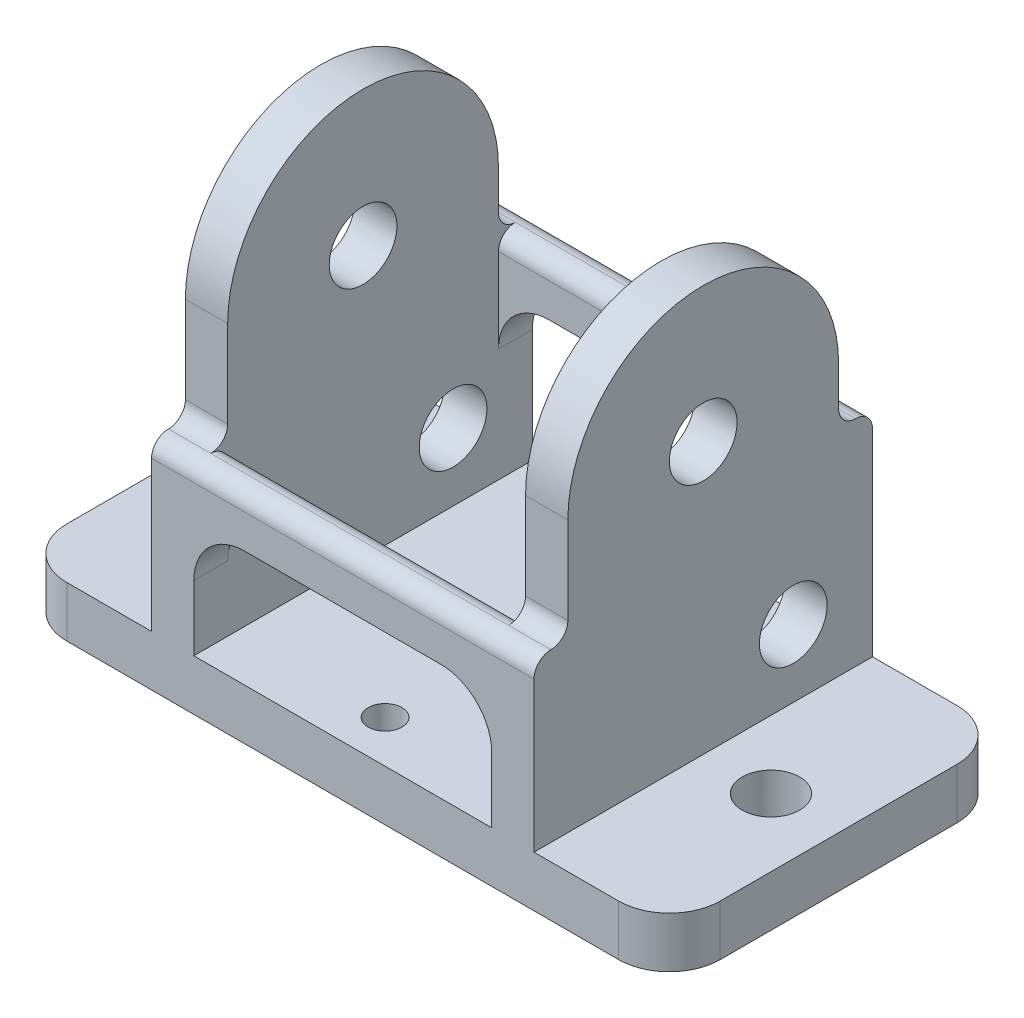
SolidWorks part; units mm, degrees
ref_plane "Plan de face" through (0, 0, 0) normal (0, 0, 1) x (1, 0, 0)
ref_plane "Plan de dessus" through (0, 0, 0) normal (0, 1, 0) x (1, 0, 0)
ref_plane "Plan de droite" through (0, 0, 0) normal (1, 0, 0) x (0, 0, -1)
sketch "Esquisse2" plane through (0, 0, 0) normal (0, 0, 1) x (1, 0, 0)
  line L0 (0, 1.475) -> (0, -1.8592) construction
  line L1 (-2.1467, 0) -> (3.7613, 0) construction
  line L4 (8.8, 2) -> (11.3, 2)
  line L5 (11.3, 2) -> (11.3, 8)
  line L6 (11.3, 8) -> (8.8, 8)
  line L7 (8.8, 8) -> (8.8, 2)
  dimension "D1" = 2.5
  dimension "D2" = 2
  dimension "D5" = 8
  dimension "D6" = 8.8
revolve "Révolution1" add sketch "Esquisse2" angle 360 about L1
sketch "Esquisse3" plane through (11.3, 0, 0) normal (1, 0, 0) x (0, 0, -1)
  line L1 (-10, -19) -> (10, -19)
  line L3 (-10, -16) -> (10, -16)
  line L4 (3.318, 0) -> (3.318, -16) construction
  line L5 (8, 0) -> (8, -6.3137)
  line L6 (5.6569, -5.6569) -> (12.7279, 1.4142) construction
  line L7 (0, -8) -> (10, -8) construction
  line L8 (8, -3.3137) -> (10, -3.3137)
  line L9 (10, -3.3137) -> (10, -19)
  line L10 (8, -6.3137) -> (10, -6.3137)
  line L11 (-5.6569, -5.6569) -> (-12.7279, 1.4142) construction
  line L12 (-8, -6.1421) -> (-10, -6.1421)
  line L13 (-12.7279, -1.4142) -> (-6.1421, -8) construction
  line L14 (-8, 0) -> (-8, -9.1421)
  line L15 (-8, -9.1421) -> (-10, -9.1421)
  line L16 (-10, -6.1421) -> (-10, -19)
  circle A0 centre (0, 0) radius 8 construction
  arc A1 (-8, 0) -> (8, 0) centre (0, 0) ccw
  circle A2 centre (0, 0) radius 3.318 construction
  circle A3 centre (5.318, -12) radius 2
  circle M5 centre (0, 0) radius 8
  dimension "D3" = 6.636
  dimension "D4" = 4
  dimension "D5" = 2
  dimension "D1" = 2
  dimension "D2" = 3
  dimension "D6" = 45
  dimension "D7" = 10
  dimension "D8" = 2
  dimension "D9" = 3
  dimension "D10" = 2
  dimension "D11" = 45
  dimension "D12" = 2
  dimension "D13" = 3
extrude "Boss.-Extru.1" add sketch "Esquisse3" against normal up to surface (2.5 mm away) contours L3 L1 | L3 M5 | L5 L10 L9 L8 | L12 L16 L15 L14 region at (11.3, -17.5, 0) region at (11.3, -11.0485, 0.0904) region at (11.3, -7.6421, 9) region at (11.3, -4.8137, -9) up to face at (8.8, 0, 2)
extrude "Boss.-Extru.2" add sketch "Esquisse3<3>" against normal up to surface (11.3 mm away) from surface contours L3 L1 | L5 L10 L9 L8 | L12 L16 L15 L14 region at (11.3, -17.5, 0) region at (11.3, -7.6421, 9) region at (11.3, -4.8137, -9) up to plane "Plan de droite" starting at face at (8.8, 0, 2)
sketch "Esquisse3<3>" plane through (11.3, 0, 0) normal (1, 0, 0) x (0, 0, -1) same geometry as "Esquisse3"
extrude "Boss-Extrude1" add sketch "Esquisse3<5>" along normal blind 8 contours L3 L16 L1 L9 region at (11.3, -17.5, 0)
sketch "Esquisse3<5>" plane through (11.3, 0, 0) normal (1, 0, 0) x (0, 0, -1) same geometry as "Esquisse3"
sketch "Sketch4" plane through (0, -16, 0) normal (0, 1, 0) x (1, 0, 0)
  line L0 (19.3, 10) -> (11.3, 10) construction
  circle A0 centre (15.3, 0) radius 1.7
  point P6 (15.3, 10)
  dimension "D1" = 3.4
extrude "Cut-Extrude1" cut sketch "Sketch4" against normal up to next
mirror "Symétrie1" about plane through (0, 0, 0) normal (1, 0, 0) of bodies 110 103
sketch "Sketch1" plane through (0, -16, 0) normal (0, 1, 0) x (1, 0, 0)
  point P3 (0, -7.5)
  dimension "D1" = 7.5
hole_wizard "Trous de centrage Ø2.0mm1" positions "Sketch1" profile "Sketch3" hole size "Ø2.0" standard "Ansi Metric" end condition up to next
sketch "Sketch3" plane through (0, -16, 7.5) normal (1, 0, 0) x (0, 0, 1)
  line L0 (0, 0) -> (0, 3)
  line L1 (0, 3) -> (1, 3)
  line L2 (1, 3) -> (1, 0)
  line L5 (1, 0) -> (0, 0)
  line L11 (0, -6.35) -> (0, 107.95) construction
  dimension "Thru Hole Dia." = 2
  dimension "Thru Hole Depth" = 3
fillet "Fillet1" radius 1 4 edges at (-10.05, -3.3137, -8) (10.05, -3.3137, -8) (-10.05, -6.1421, 8) (10.05, -6.1421, 8)
fillet "Fillet2" radius 1 4 edges at (0, -3.3137, -8) (0, -3.3137, -10) (0, -6.1421, 10) (0, -6.1421, 8)
fillet "Fillet3" radius 3 8 edges at (-8.8, -6.3137, -9) (8.8, -6.3137, -9) (8.8, -9.1421, 9) (-8.8, -9.1421, 9) (-19.3, -17.5, 10) (-19.3, -17.5, -10) (19.3, -17.5, -10) (19.3, -17.5, 10)
